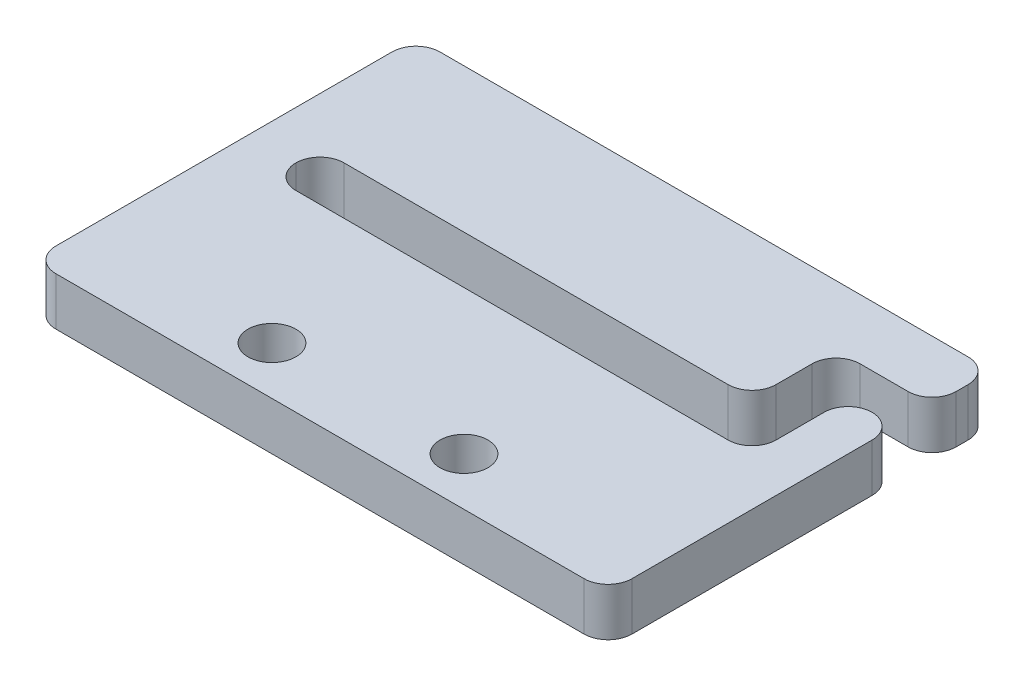
SolidWorks part; units mm, degrees
ref_plane "Front Plane" through (0, 0, 0) normal (0, 0, 1) x (1, 0, 0)
ref_plane "Top Plane" through (0, 0, 0) normal (0, 1, 0) x (1, 0, 0)
ref_plane "Right Plane" through (0, 0, 0) normal (1, 0, 0) x (0, 0, -1)
sketch "Sketch1" plane through (0, 0, 0) normal (0, 1, 0) x (1, 0, 0)
  line L0 (76.2, -7.9375) -> (63.5, -7.9375)
  line L1 (0, 0) -> (76.2, 0)
  line L2 (0, 0) -> (0, -50.8)
  line L3 (0, -50.8) -> (76.2, -50.8)
  line L4 (76.2, 0) -> (76.2, -50.8)
  line L5 (63.5, -7.9375) -> (63.5, -19.05)
  line L6 (63.5, -19.05) -> (6.35, -19.05)
  line L7 (6.35, -19.05) -> (6.35, -25.4)
  line L8 (6.35, -25.4) -> (69.85, -25.4)
  line L9 (69.85, -25.4) -> (69.85, -12.7)
  line L10 (69.85, -12.7) -> (76.2, -12.7)
  line L11 (25.4, -44.45) -> (50.8, -44.45) construction
  circle A0 centre (25.4, -44.45) radius 3.175
  circle A1 centre (50.8, -44.45) radius 3.175
  point P18 (38.1, -50.8)
  point P20 (38.1, -44.45)
  dimension "D11" = 6.35
  dimension "D1" = 76.2
  dimension "D2" = 50.8
  dimension "D3" = 25.4
  dimension "D4" = 6.35
  dimension "D5" = 6.35
  dimension "D6" = 6.35
  dimension "D7" = 4.7625
  dimension "D8" = 6.35
  dimension "D9" = 12.7
  dimension "D10" = 25.4
  dimension "D12" = 6.35
extrude "Boss-Extrude1" add sketch "Sketch1" along normal blind 6.35
fillet "Fillet1" radius 3.175 2 edges at (6.35, 3.175, 19.05) (6.35, 3.175, 25.4)
fillet "Fillet2" radius 3.175 4 edges at (76.2, 3.175, 50.8) (0, 3.175, 50.8) (0, 3.175, 0) (76.2, 3.175, 0)
fillet "Fillet3" radius 3.175 5 edges at (69.85, 3.175, 25.4) (63.5, 3.175, 7.9375) (63.5, 3.175, 19.05) (76.2, 3.175, 7.9375) (76.2, 3.175, 12.7)
fillet "Fillet4" radius 3.175 1 edges at (69.85, 3.175, 12.7)
